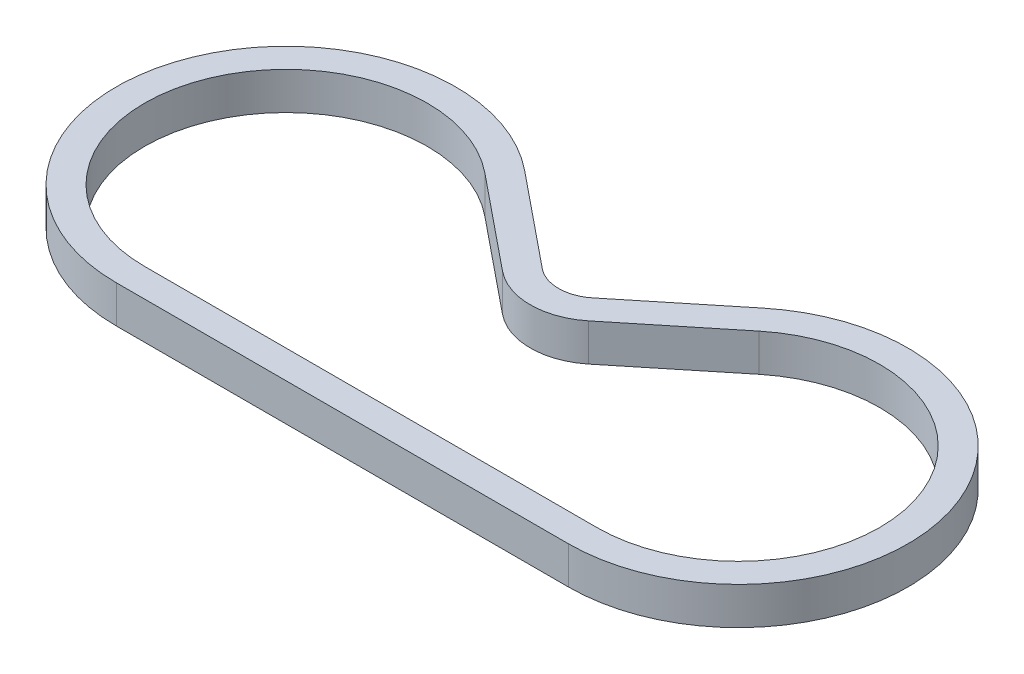
SolidWorks part; units mm, degrees
material "6061 Alloy"
ref_plane "Front Plane" through (0, 0, 0) normal (0, 0, 1) x (1, 0, 0)
ref_plane "Top Plane" through (0, 0, 0) normal (0, 1, 0) x (1, 0, 0)
ref_plane "Right Plane" through (0, 0, 0) normal (1, 0, 0) x (0, 0, -1)
sketch "Sketch1" plane through (0, 0, 0) normal (0, 1, 0) x (1, 0, 0)
  line L0 (-47.1, 0) -> (47.1, 0) construction
  line L1 (-47.1, 0) -> (47.1, 0) construction
  line L3 (-47.1, -35.3387) -> (47.1, -35.3387)
  line L4 (-47.1, 0) -> (47.1, 0) construction
  line L6 (-47.1, -29.4459) -> (47.1, -29.4459)
  line L7 (-47.1, 29.4459) -> (-47.1, 35.3387) construction
  line L8 (0, 0) -> (0, 18) construction
  line L9 (-26.6827, 25.1475) -> (-7.1033, 9.251) construction
  line L10 (-28.5399, 22.8601) -> (-8.9605, 6.9636)
  line L11 (-24.8256, 27.4349) -> (-5.2462, 11.5384)
  line L12 (28.5399, 22.8601) -> (8.9605, 6.9636)
  line L13 (24.8256, 27.4349) -> (5.2462, 11.5384)
  arc A0 (-47.1, 35.3387) -> (-47.1, -35.3387) centre (-47.1, 0) ccw
  arc A1 (47.1, -35.3387) -> (47.1, 35.3387) centre (47.1, 0) ccw
  arc A2 (-47.1, 29.4459) -> (-47.1, -29.4459) centre (-47.1, 0) ccw
  arc A3 (47.1, -29.4459) -> (47.1, 29.4459) centre (47.1, 0) ccw
  arc A4 (-7.1033, 9.251) -> (7.1033, 9.251) centre (0, 18) ccw construction
  arc A5 (-47.1, 32.3923) -> (-26.6827, 25.1475) centre (-47.1, 0) cw construction
  arc A6 (-47.1, 29.4459) -> (-28.5399, 22.8601) centre (-47.1, 0) cw
  arc A7 (-8.9605, 6.9636) -> (8.9605, 6.9636) centre (0, 18) ccw
  arc A8 (-47.1, 35.3387) -> (-24.8256, 27.4349) centre (-47.1, 0) cw
  arc A9 (-5.2462, 11.5384) -> (5.2462, 11.5384) centre (0, 18) ccw
  arc A10 (-7.1033, 9.251) -> (7.1787, 9.3127) centre (0, 18) ccw construction
  arc A11 (-8.9605, 6.9636) -> (9.0556, 7.0415) centre (0, 18) ccw construction
  arc A12 (-5.2462, 11.5384) -> (5.3019, 11.584) centre (0, 18) ccw construction
  arc A13 (28.5399, 22.8601) -> (47.1, 29.4459) centre (47.1, 0) cw
  arc A14 (24.8256, 27.4349) -> (47.1, 35.3387) centre (47.1, 0) cw
  point P0 (0, 0)
  point P4 (0, 0)
  point P10 (0, 0)
  point P11 (47.1, -35.3387)
  point P18 (-47.1, 32.3923)
  dimension "D2" = 32.3923
  dimension "D3" = 5.8928
  dimension "D4" = 11.2696
  dimension "D1" = 94.2
  dimension "D5" = 18
extrude "Boss-Extrude1" add sketch "Sketch1" along normal blind 7.7978 contours A14 L13 A9 L11 A8 A0 L3 A1 L12 A13 A3 L6 A2 A6 L10 A7
